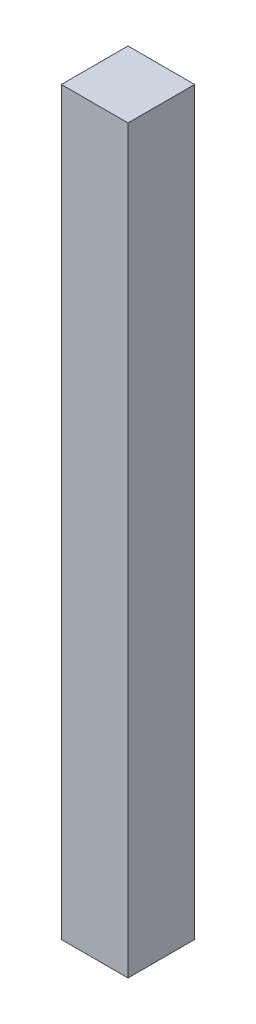
SolidWorks part; units mm, degrees
material "6061 Alloy"
ref_plane "Front Plane" through (0, 0, 0) normal (0, 0, 1) x (1, 0, 0)
ref_plane "Top Plane" through (0, 0, 0) normal (0, 1, 0) x (1, 0, 0)
ref_plane "Right Plane" through (0, 0, 0) normal (1, 0, 0) x (0, 0, -1)
sketch "Sketch1" plane through (0, 0, 0) normal (0, 1, 0) x (1, 0, 0)
  line L1 (-3.15, 3.15) -> (3.15, 3.15)
  line L2 (-3.15, 3.15) -> (-3.15, -3.15)
  line L3 (-3.15, -3.15) -> (3.15, -3.15)
  line L4 (3.15, 3.15) -> (3.15, -3.15)
  line L5 (-3.15, 3.15) -> (3.15, -3.15) construction
  line L6 (-3.15, -3.15) -> (3.15, 3.15) construction
  point P0 (0, 0)
  dimension "D1" = 6.3
extrude "Boss-Extrude1" add sketch "Sketch1" along normal blind 70
